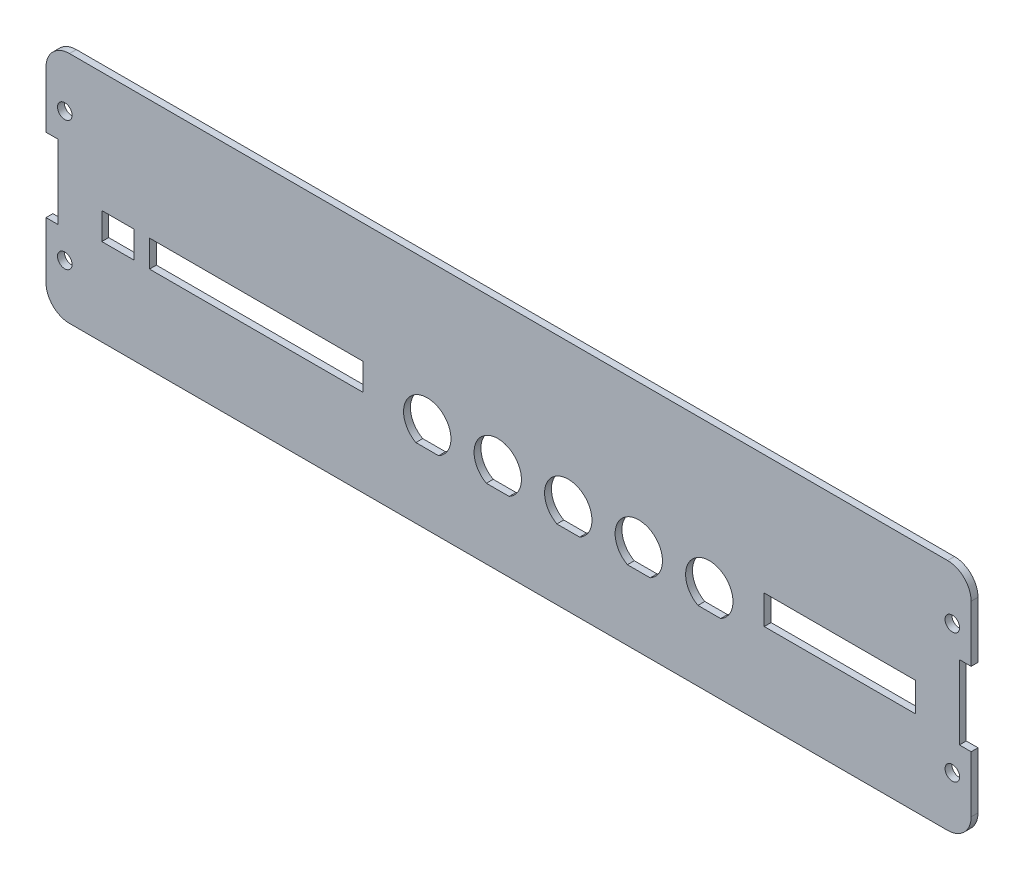
SolidWorks part; units mm, degrees
ref_plane "Front Plane" through (0, 0, 0) normal (0, 0, 1) x (1, 0, 0)
ref_plane "Top Plane" through (0, 0, 0) normal (0, 1, 0) x (1, 0, 0)
ref_plane "Right Plane" through (0, 0, 0) normal (1, 0, 0) x (0, 0, -1)
sketch "Sketch2" plane through (0, 0, 0) normal (0, 0, 1) x (1, 0, 0)
  line L0 (118.618, 31.5722) -> (-118.618, 31.5722)
  line L1 (-124.968, 25.2222) -> (-124.968, 9.9822)
  line L2 (-124.968, 9.9822) -> (-121.793, 9.9822)
  line L3 (-121.793, 9.9822) -> (-121.793, -9.9822)
  line L4 (0, 0) -> (0, 31.5722) construction
  line L5 (0, 0) -> (-121.793, 0) construction
  line L6 (124.968, 25.2222) -> (124.968, 9.9822)
  line L7 (124.968, 9.9822) -> (121.793, 9.9822)
  line L8 (121.793, 9.9822) -> (121.793, -9.9822)
  line L9 (124.968, -9.9822) -> (121.793, -9.9822)
  line L10 (124.968, -25.2222) -> (124.968, -9.9822)
  line L11 (-124.968, -9.9822) -> (-121.793, -9.9822)
  line L12 (-124.968, -25.2222) -> (-124.968, -9.9822)
  line L13 (118.618, -31.5722) -> (-118.618, -31.5722)
  arc A0 (-124.968, 25.2222) -> (-118.618, 31.5722) centre (-118.618, 25.2222) cw
  arc A1 (124.968, 25.2222) -> (118.618, 31.5722) centre (118.618, 25.2222) ccw
  arc A2 (124.968, -25.2222) -> (118.618, -31.5722) centre (118.618, -25.2222) cw
  arc A3 (-124.968, -25.2222) -> (-118.618, -31.5722) centre (-118.618, -25.2222) ccw
  point P22 (121.793, 0)
  point P25 (-124.968, -17.6022)
  dimension "D1" = 6.35
  dimension "D2" = 3.175
  dimension "D3" = 21.59
  dimension "D4" = 9.9822
  dimension "D5" = 249.936
extrude "MainBody" add sketch "Sketch2" along normal blind 1.8542
sketch "Sketch3" plane through (0, 0, 1.8542) normal (0, 0, 1) x (1, 0, 0)
  line L0 (118.618, 31.5722) -> (-118.618, 31.5722) construction
  line L2 (0, 31.5722) -> (0, 0) construction
  line L3 (0, 0) -> (-121.793, 0) construction
  line L4 (-121.793, 9.9822) -> (-121.793, -9.9822) construction
  circle A0 centre (-119.888, 17.4625) radius 1.9685
  circle A1 centre (119.888, 17.4625) radius 1.9685
  circle A2 centre (119.888, -17.4625) radius 1.9685
  circle A3 centre (-119.888, -17.4625) radius 1.9685
  dimension "D1" = 3.937
  dimension "D2" = 17.4625
  dimension "D3" = 119.888
extrude "MountHoles" cut sketch "Sketch3" against normal through all
ref_axis "MntTopLeft" through (-119.888, 17.4625, 0) along (0, 0, 1)
ref_axis "MntBottomLeft" through (-119.888, -17.4625, 0) along (0, 0, 1)
ref_axis "MntTopRight" through (119.888, 17.4625, 0) along (0, 0, 1)
ref_axis "MntBottomRight" through (119.888, -17.4625, 0) along (0, 0, 1)
ref_plane "ExtFront" through (0, 0, 1.8542) normal (0, 0, 1) x (1, 0, 0)
ref_plane "IntFront" through (0, 0, 0) normal (0, 0, -1) x (-1, 0, 0)
ref_plane "TBCenter" through (0, 0, 0) normal (0, 1, 0) x (1, 0, 0)
ref_plane "LRCenter" through (0, 0, 0) normal (-1, 0, 0) x (0, 0, 1)
sketch "Sketch4" plane through (0, 0, 1.8542) normal (0, 0, 1) x (1, 0, 0)
  line L12 (51.1533, -12.6575) -> (57.3047, -12.6575)
  line L13 (51.1533, -12.6575) -> (57.3047, -12.6575)
  line L14 (69.068, -0.7936) -> (69.068, -8.6476)
  line L15 (110.002, -0.7936) -> (69.068, -0.7936)
  line L16 (110.002, -8.6476) -> (110.002, -0.7936)
  line L17 (69.068, -8.6476) -> (110.002, -8.6476)
  line L18 (69.068, -0.7936) -> (69.068, -8.6476)
  line L19 (110.002, -0.7936) -> (69.068, -0.7936)
  line L20 (110.002, -8.6476) -> (110.002, -0.7936)
  line L21 (69.068, -8.6476) -> (110.002, -8.6476)
  line L24 (32.1033, -12.6575) -> (38.2547, -12.6575)
  line L25 (32.1033, -12.6575) -> (38.2547, -12.6575)
  line L28 (13.0533, -12.6575) -> (19.2047, -12.6575)
  line L29 (13.0533, -12.6575) -> (19.2047, -12.6575)
  line L31 (-5.9967, -12.6575) -> (0.1547, -12.6575)
  line L32 (-5.9967, -12.6575) -> (0.1547, -12.6575)
  line L35 (-25.0467, -12.6575) -> (-18.8953, -12.6575)
  line L36 (-25.0467, -12.6575) -> (-18.8953, -12.6575)
  line L73 (-96.998, -0.7936) -> (-96.998, -8.0476)
  line L74 (-39.344, -0.7936) -> (-96.998, -0.7936)
  line L75 (-96.998, -8.0476) -> (-39.344, -8.0476)
  line L76 (-39.344, -8.0476) -> (-39.344, -0.7936)
  line L77 (-96.998, -0.7936) -> (-96.998, -8.0476)
  line L78 (-39.344, -0.7936) -> (-96.998, -0.7936)
  line L79 (-96.998, -8.0476) -> (-39.344, -8.0476)
  line L80 (-39.344, -8.0476) -> (-39.344, -0.7936)
  line L91 (-109.892, -0.7936) -> (-109.892, -8.0476)
  line L92 (-101.238, -0.7936) -> (-109.892, -0.7936)
  line L93 (-101.238, -8.0476) -> (-101.238, -0.7936)
  line L94 (-109.892, -8.0476) -> (-101.238, -8.0476)
  line L95 (-109.892, -0.7936) -> (-109.892, -8.0476)
  line L96 (-101.238, -0.7936) -> (-109.892, -0.7936)
  line L97 (-101.238, -8.0476) -> (-101.238, -0.7936)
  line L98 (-109.892, -8.0476) -> (-101.238, -8.0476)
  arc A3 (57.3047, -12.6575) -> (51.1533, -12.6575) centre (54.229, -7.0441) ccw
  arc A4 (57.3047, -12.6575) -> (51.1533, -12.6575) centre (54.229, -7.0441) ccw
  arc A6 (38.2547, -12.6575) -> (32.1033, -12.6575) centre (35.179, -7.0441) ccw
  arc A7 (38.2547, -12.6575) -> (32.1033, -12.6575) centre (35.179, -7.0441) ccw
  arc A9 (19.2047, -12.6575) -> (13.0533, -12.6575) centre (16.129, -7.0441) ccw
  arc A10 (19.2047, -12.6575) -> (13.0533, -12.6575) centre (16.129, -7.0441) ccw
  arc A13 (0.1547, -12.6575) -> (-5.9967, -12.6575) centre (-2.921, -7.0441) ccw
  arc A14 (0.1547, -12.6575) -> (-5.9967, -12.6575) centre (-2.921, -7.0441) ccw
  arc A16 (-18.8953, -12.6575) -> (-25.0467, -12.6575) centre (-21.971, -7.0441) ccw
  arc A17 (-18.8953, -12.6575) -> (-25.0467, -12.6575) centre (-21.971, -7.0441) ccw
  dimension "D3" = 0.254
  dimension "D5" = 0.254
  dimension "D6" = 0.254
  dimension "D7" = 0.254
  dimension "D8" = 0.254
extrude "PanelCutout" cut sketch "Sketch4" against normal up to next
equation "\"MainBodyExtWidth\"=9.84"
equation "\"MainBodyExtHeight\"=2.52"
equation "\"D4@Sketch2\"=0.786/2in"
equation "\"D5@Sketch2\"=\"MainBodyExtWidth\""
equation "\"MainBodyThickness\"= 0.073"
equation "\"D1@MainBody\" = \"MainBodyThickness\""
equation "\"ScrewMountSize\"=0.155"
equation "\"D1@Sketch3\"=\"ScrewMountSize\""
equation "\"Tolerance\"=0.01"
equation "\"D2@Sketch4\"=\"Tolerance\""
equation "\"D3@Sketch4\"=\"Tolerance\""
equation "\"D4@Sketch4\"=\"Tolerance\""
equation "\"D5@Sketch4\"=\"Tolerance\""
equation "\"D6@Sketch4\"=\"Tolerance\""
equation "\"D7@Sketch4\"=\"Tolerance\""
equation "\"D8@Sketch4\"=\"Tolerance\""
equation "\"D1@Sketch4\"=\"Tolerance\""
